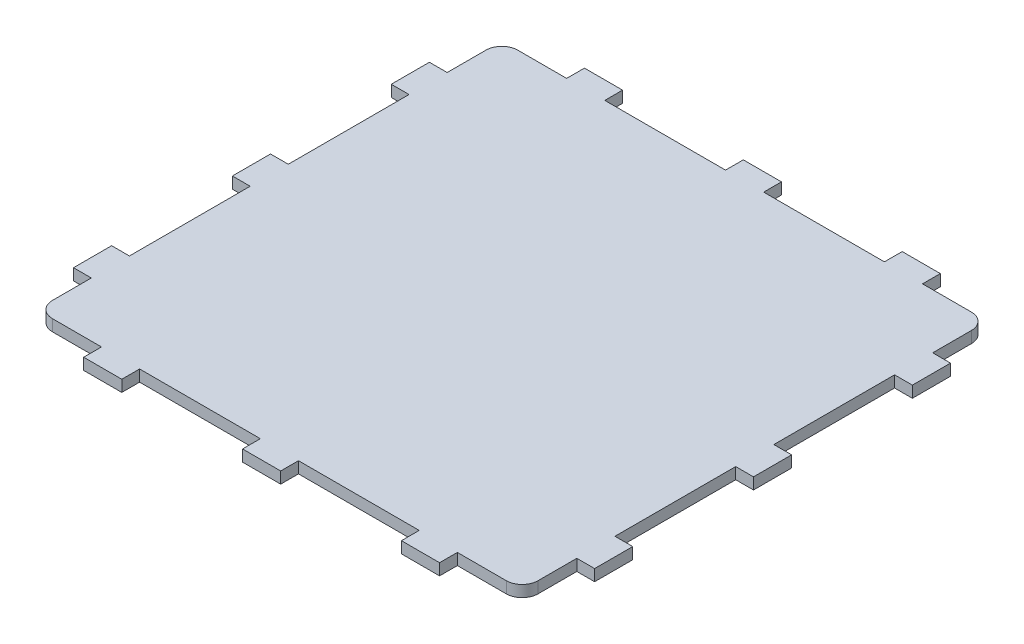
SolidWorks part; units mm, degrees
ref_plane "前视基准面" through (0, 0, 0) normal (0, 0, 1) x (1, 0, 0)
ref_plane "上视基准面" through (0, 0, 0) normal (0, 1, 0) x (1, 0, 0)
ref_plane "右视基准面" through (0, 0, 0) normal (1, 0, 0) x (0, 0, -1)
other "Configuration Table"
sketch "草图1" plane through (0, 0, 0) normal (0, 1, 0) x (1, 0, 0)
  line L1 (-382, 366) -> (382, 366)
  line L2 (-382, 366) -> (-382, -366)
  line L3 (-382, -366) -> (382, -366)
  line L4 (382, 366) -> (382, -366)
  line L5 (-410, -220) -> (-382, -220)
  line L6 (-410, -220) -> (-410, -280)
  line L7 (-410, -280) -> (-382, -280)
  line L8 (-382, -220) -> (-382, -280)
  line L9 (-280, -394) -> (-220, -394)
  line L10 (-280, -394) -> (-280, -366)
  line L11 (-280, -366) -> (-220, -366)
  line L12 (-220, -394) -> (-220, -366)
  point P4 (-382, 0)
  point P6 (0, -366)
  point P11 (-410, -250)
  dimension "D1" = 764
  dimension "D2" = 732
  dimension "D3" = 116
  dimension "D4" = 28
  dimension "D5" = 60
  dimension "D8" = 60
  dimension "D9" = 28
  dimension "D10" = 102
extrude "凸台-拉伸1" add sketch "草图1" along normal blind 18 contours L2 L3 L4 L1
extrude "凸台-拉伸2" add sketch "草图1<3>" along normal up to surface (18 mm away) contours L6 L7 L8 L5 up to face at (0, 18, 0)
sketch "草图1<3>" plane through (0, 0, 0) normal (0, 1, 0) x (1, 0, 0) same geometry as "草图1"
pattern_linear "阵列(线性)1" count 3 spacing 250 along (0, 0, -1) of "凸台-拉伸2"
mirror "镜向1" about plane through (0, 0, 0) normal (1, 0, 0) of "阵列(线性)1", "凸台-拉伸2"
extrude "凸台-拉伸3" add sketch "草图1<5>" along normal up to surface (18 mm away) contours L9 L12 L11 L10 up to face at (0, 18, 0)
sketch "草图1<5>" plane through (0, 0, 0) normal (0, 1, 0) x (1, 0, 0) same geometry as "草图1"
pattern_linear "阵列(线性)2" count 3 spacing 250 along (1, 0, 0) of "凸台-拉伸3"
mirror "镜向2" about plane through (0, 0, 0) normal (0, 0, 1) of "阵列(线性)2", "凸台-拉伸3"
fillet "圆角1" radius 25 4 edges at (-382, 9, -366) (382, 9, -366) (382, 9, 366) (-382, 9, 366)
